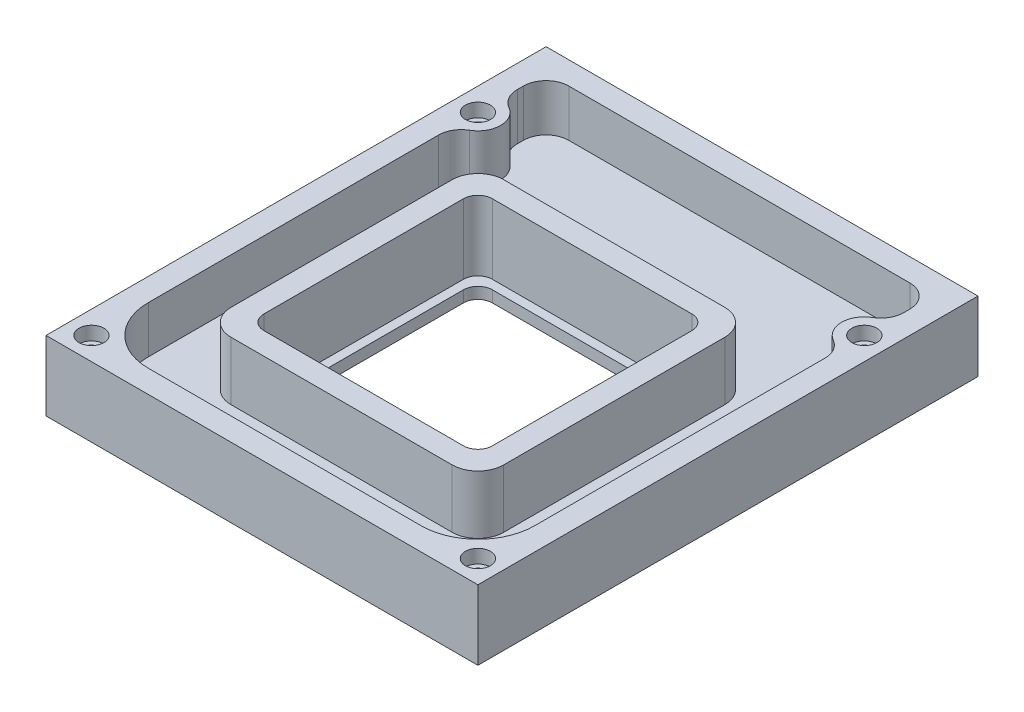
SolidWorks part; units mm, degrees
note: The reader was unsure of these and kept them because the rebuilt part matched: shared geometry of "Sketch1<3>".
ref_plane "Front Plane" through (0, 0, 0) normal (0, 0, 1) x (1, 0, 0)
ref_plane "Top Plane" through (0, 0, 0) normal (0, 1, 0) x (1, 0, 0)
ref_plane "Right Plane" through (0, 0, 0) normal (1, 0, 0) x (0, 0, -1)
sketch "Sketch1" plane through (0, 0, 0) normal (0, 1, 0) x (1, 0, 0)
  line L0 (-75, 105) -> (75, 105)
  line L1 (-60, 60) -> (60, 60)
  line L2 (-60, 60) -> (-60, -60)
  line L3 (-60, -60) -> (60, -60)
  line L4 (60, 60) -> (60, -60)
  line L5 (-50, 50) -> (50, 50)
  line L6 (-50, 50) -> (-50, -50)
  line L7 (-50, -50) -> (50, -50)
  line L8 (50, 50) -> (50, -50)
  line L10 (-75, 105) -> (-75, -75)
  line L11 (-75, -75) -> (75, -75)
  line L12 (75, 105) -> (75, -75)
  line L13 (-95, 125) -> (95, 125)
  line L14 (-95, 125) -> (-95, -95)
  line L15 (-95, -95) -> (95, -95)
  line L16 (95, 125) -> (95, -95)
  point P16 (0, 50)
  point P18 (0, 60)
  point P20 (0, 125)
  point P23 (-60, 0)
  point P24 (-50, 0)
  point P40 (0, 105)
  dimension "D1" = 100
  dimension "D2" = 45
  dimension "D3" = 15
  dimension "D4" = 10
  dimension "D5" = 15
  dimension "D6" = 20
  dimension "D7" = 20
  dimension "D8" = 20
extrude "Boss-Extrude1" add sketch "Sketch1" along normal blind 10 contours L16 L13 L14 L15 L0 L12 L11 L10 | L12 L0 L10 L11 L1 L4 L3 L2 | L4 L1 L2 L3 L5 L8 L7 L6
extrude "Boss-Extrude2" add sketch "Sketch1<3>" along normal blind 35.693 contours L16 L13 L14 L15 L0 L12 L11 L10 | L4 L1 L2 L3 L5 L8 L7 L6
sketch "Sketch1<3>" plane through (0, 0, 0) normal (0, 1, 0) x (1, 0, 0) same geometry as "Sketch1"
sketch "Sketch3" plane through (0, 35.693, 0) normal (0, 1, 0) x (1, 0, 0)
  line L1 (-95, 125) -> (95, 125)
  line L2 (-95, 125) -> (-95, -95)
  line L3 (-95, -95) -> (95, -95)
  line L4 (95, 125) -> (95, -95)
  line L5 (-75, 105) -> (75, 105)
  line L6 (-75, 105) -> (-75, -75)
  line L7 (-75, -75) -> (75, -75)
  line L8 (75, 105) -> (75, -75)
extrude "Cut-Extrude1" cut sketch "Sketch3" against normal blind 5
sketch "Sketch5" plane through (0, 0, 0) normal (0, -1, 0) x (-1, 0, 0)
  line L0 (95, 125) -> (95, -95) construction
  line L1 (-95, 125) -> (-95, -95) construction
  line L2 (95, -95) -> (-95, -95) construction
  line L3 (95, 125) -> (-95, 125) construction
  circle A0 centre (85, 85) radius 5.5565
  circle A1 centre (85, -85) radius 5.5565
  circle A2 centre (-85, -85) radius 5.5565
  circle A3 centre (-85, 85) radius 5.5565
  dimension "D1" = 11.113
  dimension "D2" = 10
  dimension "D3" = 10
  dimension "D4" = 10
  dimension "D5" = 40
extrude "Cut-Extrude2" cut sketch "Sketch5" against normal blind 22
ref_plane "Plane1" through (0, 22, 0) normal (0, -1, 0) x (-1, 0, 0)
sketch "Sketch7" plane through (0, 22, 0) normal (0, -1, 0) x (-1, 0, 0)
  circle A2 centre (85, 85) radius 3.3
  circle A3 centre (85, -85) radius 3.3
  circle A4 centre (-85, -85) radius 3.3
  circle A5 centre (-85, 85) radius 3.3
  dimension "D1" = 6.6
extrude "Cut-Extrude3" cut sketch "Sketch7" against normal through all
sketch "Sketch8" plane through (0, 10, 0) normal (0, 1, 0) x (1, 0, 0)
  line L0 (-95, -95) -> (95, -95) construction
  line L1 (85, 115) -> (-85, 115)
  line L2 (85, 115) -> (85, 95)
  line L3 (75, -85) -> (-75, -85)
  line L4 (-85, 115) -> (-85, 95)
  line L5 (-95, 125) -> (-95, -95) construction
  line L6 (95, -95) -> (95, 125) construction
  line L7 (95, 125) -> (-95, 125) construction
  line L8 (85, 75) -> (85, -75)
  line L9 (-85, 75) -> (-85, -75)
  line L10 (75, 105) -> (-75, 105) construction
  line L11 (73, 105) -> (-73, 105)
  line L12 (73, 105) -> (73, -75)
  line L13 (73, -75) -> (-73, -75)
  line L14 (-73, 105) -> (-73, -75)
  line L20 (-75, -75) -> (75, -75) construction
  arc A0 (85, 95) -> (85, 75) centre (85, 85) ccw
  arc A1 (85, -75) -> (75, -85) centre (85, -85) ccw
  arc A2 (-75, -85) -> (-85, -75) centre (-85, -85) ccw
  arc A3 (-85, 75) -> (-85, 95) centre (-85, 85) ccw
  dimension "D5" = 2
  dimension "D1" = 10
  dimension "D2" = 20
  dimension "D3" = 150
  dimension "D4" = 2
extrude "Cut-Extrude4" cut sketch "Sketch8" along normal up to next
fillet "Fillet1" radius 10 6 edges at (-85, 20.3465, -115) (85, 20.3465, -115) (-85, 20.3465, -75) (-85, 20.3465, -95) (85, 20.3465, -75) (85, 20.3465, -95)
sketch "Sketch10" plane through (0, 30.693, 0) normal (0, 1, 0) x (1, 0, 0)
  circle A0 centre (85, 85) radius 5.5
  circle A1 centre (85, -85) radius 5.5
  circle A2 centre (-85, -85) radius 5.5
  circle A3 centre (-85, 85) radius 5.5
  dimension "D1" = 11
extrude "Cut-Extrude5" cut sketch "Sketch10" against normal offset from surface (6 mm away) 2.693 up to face at (85, 22, -88.3)
sketch "Sketch11" plane through (0, 10, 0) normal (0, 1, 0) x (1, 0, 0)
  line L0 (-75, -85) -> (75, -85) construction
  line L2 (85, -75) -> (85, 67.6795) construction
  arc A0 (60, -85) -> (85, -60) centre (60, -60) ccw
  arc A1 (-85, -60) -> (-60, -85) centre (-60, -60) ccw
  arc A2 (85, -60) -> (60, -85) centre (67.7327, -67.7327) cw
  circle A3 centre (85, -85) radius 5.5 construction
  arc A4 (-60, -85) -> (-85, -60) centre (-67.7327, -67.7327) cw
  circle A5 centre (-85, -85) radius 5.5 construction
extrude "Boss-Extrude5" add sketch "Sketch11" along normal up to surface (20.693 mm away) up to face at (-85, 30.693, -79.5)
sketch "Sketch13" plane through (0, 0, 0) normal (0, 1, 0) x (1, 0, 0)
  line L15 (-50.25, -50.25) -> (50.25, -50.25)
  line L16 (-50.25, 50.25) -> (-50.25, -50.25)
  line L17 (50.25, 50.25) -> (-50.25, 50.25)
  line L18 (50.25, -50.25) -> (50.25, 50.25)
  line L19 (-50.25, -50.25) -> (50.25, -50.25)
  line L20 (-50.25, 50.25) -> (-50.25, -50.25)
  line L21 (50.25, 50.25) -> (-50.25, 50.25)
  line L22 (50.25, -50.25) -> (50.25, 50.25)
  dimension "D1" = 0.25
extrude "Cut-Extrude10" cut sketch "Sketch13" along normal up to next
fillet "Fillet2" radius 11.35 4 edges at (-60, 22.8465, -60) (-60, 22.8465, 60) (60, 22.8465, 60) (60, 22.8465, -60)
sketch "Sketch14" plane through (0, 0, 0) normal (0, 1, 0) x (1, 0, 0)
  line L0 (50.25, -50.25) -> (50.25, 50.25) construction
  line L1 (46.25, 46.25) -> (-46.25, 46.25)
  line L2 (46.25, 46.25) -> (46.25, -46.25)
  line L3 (46.25, -46.25) -> (-46.25, -46.25)
  line L4 (-46.25, 46.25) -> (-46.25, -46.25)
  line L5 (50.25, 50.25) -> (-50.25, 50.25) construction
  line L7 (-50.25, -50.25) -> (50.25, -50.25) construction
  line L8 (-50.25, 50.25) -> (-50.25, -50.25) construction
  line L10 (50.25, 50.25) -> (-50.25, 50.25)
  line L11 (50.25, 50.25) -> (50.25, -50.25)
  line L12 (50.25, -50.25) -> (-50.25, -50.25)
  line L13 (-50.25, 50.25) -> (-50.25, -50.25)
  dimension "D1" = 4
  dimension "D2" = 4
  dimension "D3" = 4
  dimension "D4" = 4
extrude "Boss-Extrude6" add sketch "Sketch14" along normal blind 5
fillet "Fillet3" radius 6.35 4 edges at (-50.25, 20.3465, 50.25) (-50.25, 20.3465, -50.25) (50.25, 20.3465, 50.25) (50.25, 20.3465, -50.25)
fillet "Fillet4" radius 6.35 4 edges at (-46.25, 2.5, -46.25) (-46.25, 2.5, 46.25) (46.25, 2.5, 46.25) (46.25, 2.5, -46.25)
equation "\"D3@Sketch5\"=\"D2@Sketch5\""
equation "\"D4@Sketch5\"=\"D2@Sketch5\""
